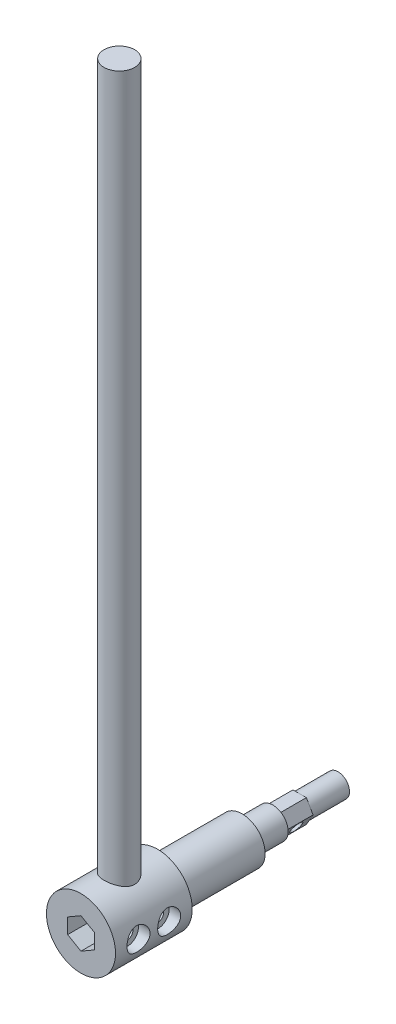
SolidWorks part; units mm, degrees
ref_plane "Front Plane" through (0, 0, 0) normal (0, 0, 1) x (1, 0, 0)
ref_plane "Top Plane" through (0, 0, 0) normal (0, 1, 0) x (1, 0, 0)
ref_plane "Right Plane" through (0, 0, 0) normal (1, 0, 0) x (0, 0, -1)
sketch "Sketch1" plane through (0, 0, 0) normal (0, 0, 1) x (1, 0, 0)
  line L3 (0, 4) -> (3.4641, 2)
  line L4 (3.4641, 2) -> (3.4641, -2)
  line L5 (3.4641, -2) -> (0, -4)
  line L12 (0, -4) -> (-3.4641, -2)
  line L13 (-3.4641, -2) -> (-3.4641, 2)
  line L14 (-3.4641, 2) -> (0, 4)
  circle A0 centre (0, 0) radius 9
  point P7 (0, 0)
  point P12 (0, 0)
  point P16 (0, 0)
extrude "Boss-Extrude1" add sketch "Sketch1" along normal blind 20
ref_plane "Plane2" through (0, 192.5, 0) normal (0, 1, 0) x (1, 0, 0)
sketch "Sketch6" plane through (0, 192.5, 0) normal (0, 1, 0) x (1, 0, 0)
  line L0 (0, 0) -> (0, -20) construction
  line L1 (-9, -20) -> (9, -20) construction
  circle A0 centre (0, -10) radius 4
extrude "Boss-Extrude3" add sketch "Sketch6" against normal up to surface (183.5 mm away) up to face at (9, 0, 20)
ref_plane "Plane4" through (0, 0, 0) normal (-1, 0, 0) x (0, 0, 1)
sketch "Sketch8" plane through (0, 0, 0) normal (-1, 0, 0) x (0, 0, 1)
  line L0 (0, 0) -> (6, 0) construction
  line L2 (0, 9) -> (0, -9) construction
  line L3 (20, 0) -> (14, 0) construction
  line L4 (20, -9) -> (20, 9) construction
  circle A0 centre (6, 0) radius 1.55
  circle A1 centre (14, 0) radius 1.55
extrude "Cut-Extrude1" cut sketch "Sketch8" against normal blind 9 and the other way blind 9
sketch "Sketch11" plane through (0, 0, 0) normal (0, 0, -1) x (-1, 0, 0)
  circle A0 centre (0, 0) radius 6
extrude "Boss-Extrude12" add sketch "Sketch11" along normal blind 22
sketch "Sketch12" plane through (0, 0, -22) normal (0, 0, -1) x (-1, 0, 0)
  circle A0 centre (0, 0) radius 4
extrude "Boss-Extrude13" add sketch "Sketch12" along normal blind 8
sketch "Sketch13" plane through (0, 0, -30) normal (0, 0, -1) x (-1, 0, 0)
  line L0 (3.5, 0) -> (-3.5, 0) construction
  line L1 (-1.75, -3.0311) -> (1.75, 3.0311) construction
  line L2 (1.75, -3.0311) -> (-1.75, 3.0311) construction
  line L3 (1.75, 3.0311) -> (-1.75, 3.0311)
  line L4 (-1.75, 3.0311) -> (-3.5, 0)
  line L5 (-3.5, 0) -> (-1.75, -3.0311)
  line L6 (-1.75, -3.0311) -> (1.75, -3.0311)
  line L7 (1.75, -3.0311) -> (3.5, 0)
  line L8 (3.5, 0) -> (1.75, 3.0311)
  point P6 (0, 0)
  point P9 (0, 0)
  point P12 (0, 0)
extrude "Boss-Extrude14" add sketch "Sketch13" along normal blind 7 contours L4 L5 L6 L7 L8 L3
sketch "Sketch14" plane through (2.625, -1.5155, 0) normal (0.866, -0.5, 0) x (0, 0, -1)
  line L0 (30, 0) -> (37, 0) construction
  line L1 (30, 1.75) -> (30, -1.75) construction
  line L2 (37, 1.75) -> (37, -1.75) construction
  circle A0 centre (33.5, 0) radius 1.55
extrude "Cut-Extrude2" cut sketch "Sketch14" against normal blind 6.1
sketch "Sketch15" plane through (0, 0, -37) normal (0, 0, -1) x (-1, 0, 0)
  circle A0 centre (0, 0) radius 3
extrude "Boss-Extrude15" add sketch "Sketch15" along normal blind 10
sketch "Sketch16" plane through (0, 0, 0) normal (-1, 0, 0) x (0, 0, 1)
  circle A1 centre (6, 0) radius 3
  circle A2 centre (14, 0) radius 3
extrude "Cut-Extrude5" cut sketch "Sketch16" against normal blind 3 from offset 9
extrude "Cut-Extrude6" cut sketch "Sketch16<2>" along normal blind 3 from offset 9 offset against normal yes
sketch "Sketch16<2>" plane through (0, 0, 0) normal (-1, 0, 0) x (0, 0, 1) same geometry as "Sketch16"
